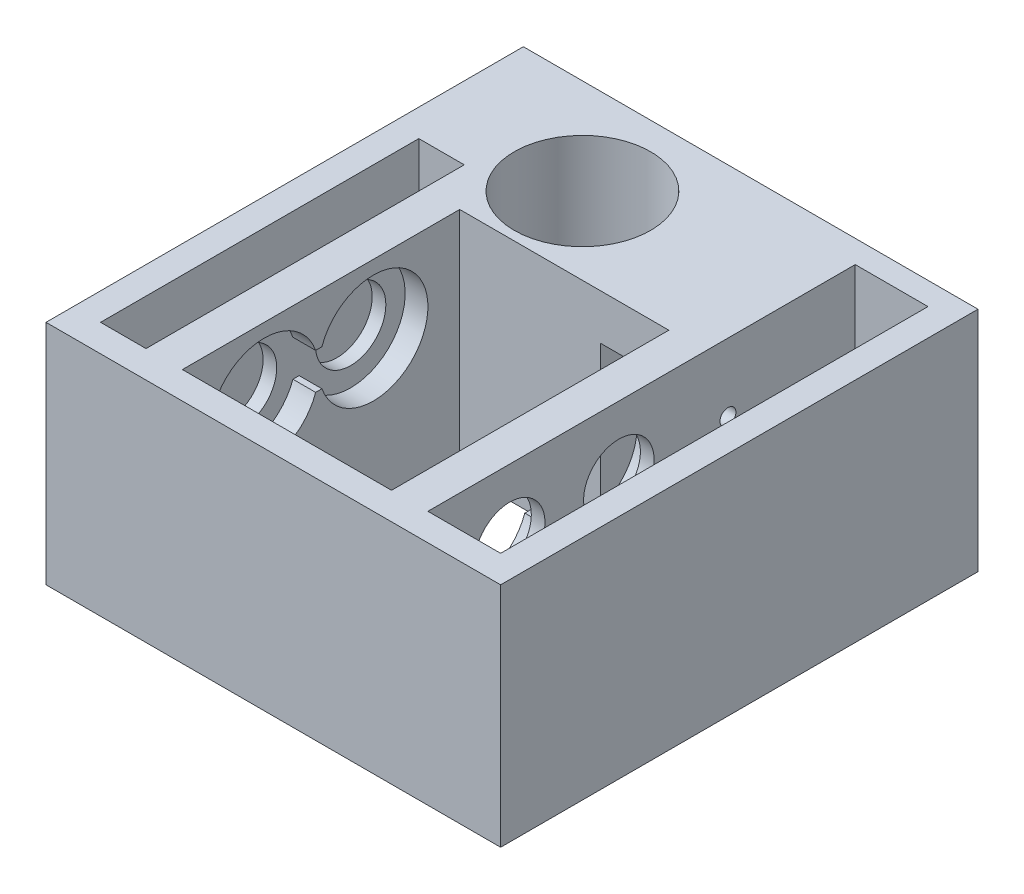
SolidWorks part; units mm, degrees
ref_plane "Front Plane" through (0, 0, 0) normal (0, 0, 1) x (1, 0, 0)
ref_plane "Top Plane" through (0, 0, 0) normal (0, 1, 0) x (1, 0, 0)
ref_plane "Right Plane" through (0, 0, 0) normal (1, 0, 0) x (0, 0, -1)
sketch "Sketch2" plane through (0, 0, 0) normal (0, 1, 0) x (1, 0, 0)
  line L0 (0, 54.9293) -> (0, -74.9036) construction
  line L1 (-50, 52.5) -> (50, 52.5)
  line L2 (-50, 52.5) -> (-50, -52.5)
  line L3 (-50, -52.5) -> (50, -52.5)
  line L4 (50, 52.5) -> (50, -52.5)
  line L5 (-72.7442, 0) -> (103.5154, 0) construction
  dimension "D1" = 105
  dimension "D2" = 100
extrude "Boss-Extrude1" add sketch "Sketch2" along normal blind 50
sketch "Sketch3" plane through (0, 50, 0) normal (0, 1, 0) x (1, 0, 0)
  line L0 (-69.2782, 0) -> (105.7343, 0) construction
  line L1 (0, 63.7563) -> (0, -72.2212) construction
  line L3 (-50, 52.5) -> (-50, -52.5) construction
  line L4 (50, 52.5) -> (-50, 52.5) construction
  circle A0 centre (-39, 0) radius 5 construction
  circle A1 centre (-39, 0) radius 39 construction
  circle A2 centre (-16.0054, 31.5) radius 15
  dimension "D1" = 10
  dimension "D2" = 6
  dimension "D3" = 78
  dimension "D4" = 30
  dimension "D5" = 6
extrude "Cut-Extrude1" cut sketch "Sketch3" against normal up to next
sketch "Sketch5" plane through (0, 50, 0) normal (0, 1, 0) x (1, 0, 0)
  line L0 (50, -52.5) -> (50, 52.5) construction
  line L1 (28, 33.5) -> (44, 33.5)
  line L2 (28, 33.5) -> (28, -46.5)
  line L3 (28, -46.5) -> (44, -46.5)
  line L4 (44, 33.5) -> (44, -46.5)
  line L5 (-44, 23.5) -> (-34, 23.5)
  line L6 (-44, 23.5) -> (-44, -46.5)
  line L7 (-44, -46.5) -> (-34, -46.5)
  line L8 (-34, 23.5) -> (-34, -46.5)
  line L9 (-50, -52.5) -> (50, -52.5) construction
  line L10 (-50, 52.5) -> (-50, -52.5) construction
  dimension "D1" = 6
  dimension "D2" = 6
  dimension "D3" = 80
  dimension "D4" = 16
  dimension "D5" = 6
  dimension "D6" = 6
  dimension "D7" = 70
  dimension "D8" = 10
extrude "Cut-Extrude3" cut sketch "Sketch5" against normal up to next
sketch "Sketch6" plane through (28, 0, 0) normal (1, 0, 0) x (0, 0, -1)
  line L0 (-16.5, 56.9811) -> (-16.5, -19.2113) construction
  line L1 (-69.1636, 35) -> (71.5534, 35) construction
  line L2 (-17.1863, 39) -> (-15.8137, 39)
  line L3 (-17.1863, 31) -> (-15.8137, 31)
  line L4 (-46.5, 0) -> (33.5, 0)
  line L5 (33.5, 0) -> (33.5, 50)
  line L6 (33.5, 50) -> (-46.5, 50)
  line L7 (-46.5, 50) -> (-46.5, 0)
  line L8 (-46.5, 0) -> (33.5, 0) construction
  line L9 (33.5, 0) -> (33.5, 50) construction
  line L10 (33.5, 50) -> (-46.5, 50) construction
  line L11 (-46.5, 50) -> (-46.5, 0) construction
  arc A0 (-17.1863, 39) -> (-17.1863, 31) centre (-28.5, 35) ccw
  circle A2 centre (-28.5, 35) radius 9 construction
  arc A3 (-15.8137, 39) -> (-15.8137, 31) centre (-4.5, 35) cw
  arc A4 (-16.5, 35) -> (-17.1863, 39) centre (-28.5, 35) ccw construction
  arc A5 (-17.1863, 31) -> (-16.5, 35) centre (-28.5, 35) ccw construction
  arc A6 (-15.8137, 31) -> (-16.5, 35) centre (-4.5, 35) cw construction
  arc A7 (-16.5, 35) -> (-15.8137, 39) centre (-4.5, 35) cw construction
  dimension "D4" = 24
  dimension "D5" = 18
  dimension "D2" = 30
  dimension "D3" = 35
  dimension "D6" = 12
  dimension "D7" = 12
  dimension "D8" = 4
  dimension "D1" = 0
extrude "Cut-Extrude4" cut sketch "Sketch6" against normal blind 31
sketch "Sketch7" plane through (28, 0, 0) normal (1, 0, 0) x (0, 0, -1)
  line L0 (-17.1863, 31) -> (-15.8137, 31) construction
  line L1 (-15.8137, 39) -> (-17.1863, 39) construction
  line L2 (-17.1863, 31) -> (-15.8137, 31)
  line L3 (-15.8137, 39) -> (-17.1863, 39)
  arc A6 (-15.8137, 31) -> (-15.8137, 39) centre (-4.5, 35) ccw construction
  arc A7 (-17.1863, 39) -> (-17.1863, 31) centre (-28.5, 35) ccw construction
  arc A8 (-15.8137, 31) -> (-15.8137, 39) centre (-4.5, 35) ccw
  arc A9 (-17.1863, 39) -> (-17.1863, 31) centre (-28.5, 35) ccw
  circle A10 centre (-28.5, 35) radius 7.75
  circle A11 centre (-4.5, 35) radius 7.75
  dimension "D1" = 15.5
  dimension "D2" = 15.5
extrude "Boss-Extrude2" add sketch "Sketch7" against normal blind 3
ref_plane "Plane1" through (-3, 0, 0) normal (1, 0, 0) x (0, 0, -1)
mirror "Mirror1" about plane through (-3, 0, 0) normal (1, 0, 0) of "Boss-Extrude2", "Cut-Extrude4"
sketch "Sketch11" plane through (0, 50, 0) normal (0, 1, 0) x (1, 0, 0)
  line L0 (50, 52.5) -> (-50, 52.5) construction
  line L1 (28, 47.5) -> (44, 47.5)
  line L2 (28, 47.5) -> (28, 33.5)
  line L3 (28, 33.5) -> (44, 33.5)
  line L4 (44, 47.5) -> (44, 33.5)
  line L5 (44, -46.5) -> (44, 33.5) construction
  line L6 (28, 33.5) -> (28, -46.5) construction
  line L7 (44, 33.5) -> (28, 33.5) construction
  dimension "D1" = 5
extrude "Cut-Extrude7" cut sketch "Sketch11" against normal up to next
sketch "Sketch8" plane through (0, 50, 0) normal (0, 1, 0) x (1, 0, 0)
  line L0 (28, 47.5) -> (28, -46.5) construction
  line L1 (-26, 14.5) -> (20, 14.5)
  line L2 (-26, 14.5) -> (-26, -46.5)
  line L3 (-26, -46.5) -> (20, -46.5)
  line L4 (20, 14.5) -> (20, -46.5)
  line L5 (-34, -46.5) -> (-34, 23.5) construction
  line L6 (-50, -52.5) -> (50, -52.5) construction
  circle A0 centre (-16.0054, 31.5) radius 15 construction
  dimension "D4" = 2
  dimension "D1" = 8
  dimension "D2" = 8
  dimension "D3" = 6
extrude "Cut-Extrude5" cut sketch "Sketch8" against normal up to next
sketch "Sketch9" plane through (28, 0, 0) normal (1, 0, 0) x (0, 0, -1)
  line L0 (-15.8137, 39) -> (-17.1863, 39) construction
  line L1 (-17.1863, 31) -> (-15.8137, 31) construction
  line L2 (-28.5, 35) -> (60.6587, 35) construction
  line L3 (-15.8137, 39) -> (-17.1863, 39) construction
  line L4 (19.5, 55.6457) -> (19.5, -7.192) construction
  line L5 (-46.5, 0) -> (47.5, 0)
  line L6 (47.5, 0) -> (47.5, 50)
  line L7 (47.5, 50) -> (-46.5, 50)
  line L12 (-46.5, 50) -> (-46.5, 0)
  line L16 (-46.5, 50) -> (-46.5, 0) construction
  line L17 (-17.1863, 31) -> (-15.8137, 31) construction
  line L18 (52.5, 50) -> (52.5, 0) construction
  line L21 (47.5, 0) -> (47.5, 50) construction
  arc A1 (-17.1863, 39) -> (-17.1863, 31) centre (-28.5, 35) ccw construction
  circle A7 centre (19.5, 35) radius 12 construction
  arc A15 (-15.8137, 31) -> (-15.8137, 39) centre (-4.5, 35) ccw construction
  arc A16 (-17.1863, 39) -> (-17.1863, 31) centre (-28.5, 35) ccw construction
  arc A17 (-15.8137, 31) -> (-15.8137, 39) centre (-4.5, 35) ccw construction
  circle A18 centre (19.5, 35) radius 1.75
  dimension "D2" = 24
  dimension "D3" = 3.5
  dimension "D4" = 33
  dimension "D1" = 0
extrude "Cut-Extrude8" cut sketch "Sketch9" against normal blind 3
sketch "Sketch13" plane through (0, 0, 0) normal (0, -1, 0) x (1, 0, 0)
  line L0 (-62.8638, -19.5) -> (95.3177, -19.5) construction
  line L1 (5, -14.5) -> (25, -14.5)
  line L2 (5, -14.5) -> (5, -33.5)
  line L3 (5, -33.5) -> (25, -33.5)
  line L4 (25, -14.5) -> (25, -33.5)
  line L5 (50, -52.5) -> (-50, -52.5) construction
  line L6 (28, 46.5) -> (28, -47.5) construction
  dimension "D1" = 19
  dimension "D2" = 20
  dimension "D3" = 33
  dimension "D4" = 5
  dimension "D5" = 3
extrude "Cut-Extrude9" cut sketch "Sketch13" against normal blind 40
